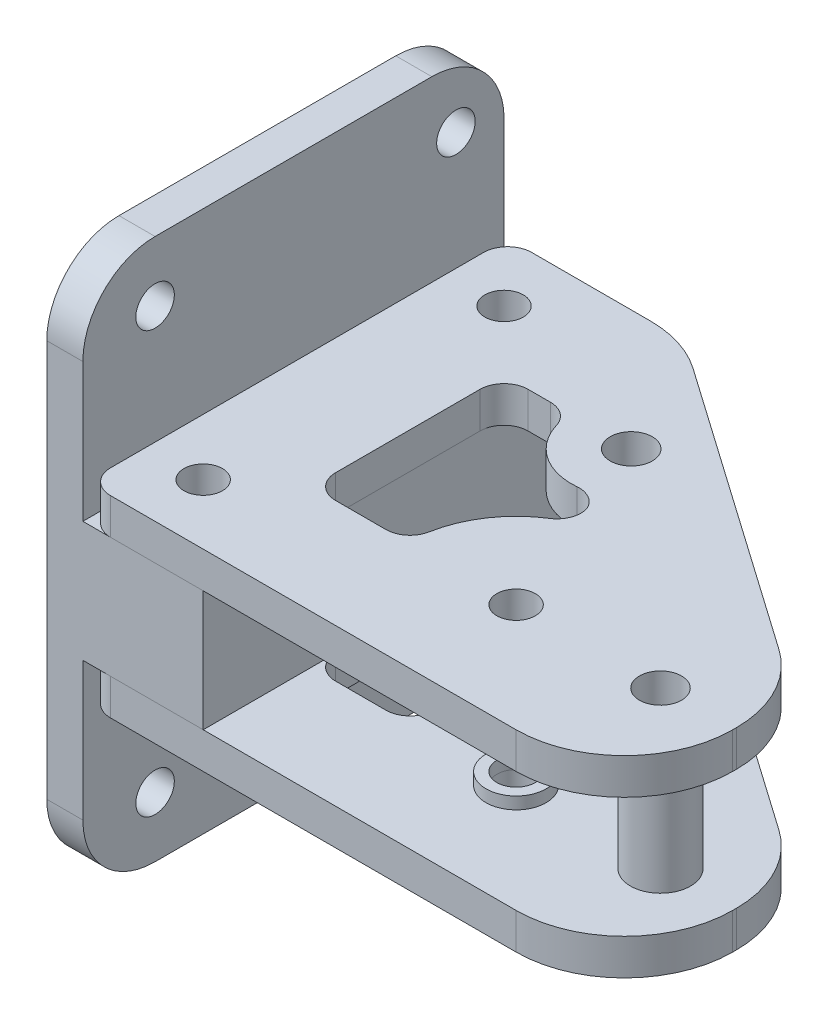
SolidWorks part; units mm, degrees
ref_plane "前视基准面" through (0, 0, 0) normal (0, 0, 1) x (1, 0, 0)
ref_plane "上视基准面" through (0, 0, 0) normal (0, 1, 0) x (1, 0, 0)
ref_plane "右视基准面" through (0, 0, 0) normal (1, 0, 0) x (0, 0, -1)
sketch "草图1" plane through (-18, 0, 0) normal (1, 0, 0) x (0, 0, -1)
  line L5 (-12.5, -18.5) -> (10.5, -18.5)
  line L6 (16.5, -12.5) -> (16.5, 20.5)
  line L7 (10.5, 26.5) -> (-12.5, 26.5)
  line L8 (-18.5, 20.5) -> (-18.5, -12.5)
  line L9 (-12.5, -18.5) -> (10.5, -18.5)
  line L10 (16.5, -12.5) -> (16.5, 20.5)
  line L11 (10.5, 26.5) -> (-12.5, 26.5)
  line L12 (-18.5, 20.5) -> (-18.5, -12.5)
  circle A0 centre (-12.5, -13.5) radius 1.6 construction
  circle A1 centre (12.5, -13.5) radius 1.6 construction
  circle A2 centre (12.5, 21.5) radius 1.6 construction
  circle A3 centre (-12.5, 21.5) radius 1.6 construction
  arc A4 (10.5, -18.5) -> (16.5, -12.5) centre (10.5, -12.5) ccw
  arc A5 (16.5, 20.5) -> (10.5, 26.5) centre (10.5, 20.5) ccw
  arc A6 (-12.5, 26.5) -> (-18.5, 20.5) centre (-12.5, 20.5) ccw
  arc A7 (-18.5, -12.5) -> (-12.5, -18.5) centre (-12.5, -12.5) ccw
  arc A8 (10.5, -18.5) -> (16.5, -12.5) centre (10.5, -12.5) ccw
  arc A9 (16.5, 20.5) -> (10.5, 26.5) centre (10.5, 20.5) ccw
  arc A10 (-12.5, 26.5) -> (-18.5, 20.5) centre (-12.5, 20.5) ccw
  arc A11 (-18.5, -12.5) -> (-12.5, -18.5) centre (-12.5, -12.5) ccw
  circle A12 centre (-12.5, -13.5) radius 1.6
  circle A13 centre (12.5, -13.5) radius 1.6
  circle A14 centre (12.5, 21.5) radius 1.6
  circle A15 centre (-12.5, 21.5) radius 1.6
  dimension "D1" = 0
extrude "凸台-拉伸1" add sketch "草图1" along normal blind 3
sketch "草图2" plane through (-15, 0, 0) normal (1, 0, 0) x (0, 0, -1)
  line L0 (-18.5, 4) -> (16.5, 4) construction
  line L1 (-18.5, 20.5) -> (-18.5, -12.5) construction
  line L2 (16.5, -12.5) -> (16.5, 20.5) construction
  line L3 (-1, 26.5) -> (-1, -18.5) construction
  line L4 (10.5, 26.5) -> (-12.5, 26.5) construction
  line L5 (-12.5, -18.5) -> (10.5, -18.5) construction
  line L7 (-18.5, -1) -> (16.5, -1)
  line L8 (-18.5, -1) -> (-18.5, 9)
  line L9 (-18.5, 9) -> (16.5, 9)
  line L10 (16.5, -1) -> (16.5, 9)
  line L11 (-18.5, -1) -> (16.5, 9) construction
  line L12 (-18.5, 9) -> (16.5, -1) construction
  point P12 (-1, 4)
  dimension "D1" = 10
extrude "凸台-拉伸2" add sketch "草图2" along normal blind 10
sketch "草图4" plane through (0, -1, 0) normal (0, -1, 0) x (1, 0, 0)
  line L0 (-10, 18.5) -> (-10, -16.5) construction
  line L1 (-5, 18.5) -> (-15, 18.5) construction
  line L2 (-5, -16.5) -> (-15, -16.5) construction
  line L3 (-5, 1) -> (-15, 1) construction
  line L4 (-5, 18.5) -> (-5, -16.5) construction
  line L5 (-15, 12.5) -> (-15, -10.5) construction
  circle A0 centre (-10, 13.5) radius 1.6
  circle A1 centre (-10, -11.5) radius 1.6
  dimension "D1" = 3.2
  dimension "D2" = 25
extrude "切除-拉伸2" cut sketch "草图4" against normal up to next
sketch "草图6" plane through (0, -1, 0) normal (0, -1, 0) x (1, 0, 0)
  line L0 (-15, 18.5) -> (30, 18.5)
  line L1 (30, 18.5) -> (30, 4.5)
  line L2 (30, 4.5) -> (0, -16.5)
  line L3 (0, -16.5) -> (-15, -16.5)
  line L4 (-15, -16.5) -> (-15, 18.5)
  line L5 (-5, 18.5) -> (-5, -16.5) construction
  circle A0 centre (-10, -11.5) radius 1.6 construction
  circle A2 centre (-10, 13.5) radius 1.6 construction
  circle A3 centre (-10, -11.5) radius 1.6
  circle A5 centre (-10, 13.5) radius 1.6
  dimension "D1" = 35
  dimension "D2" = 15
  dimension "D3" = 14
extrude "凸台-拉伸3" add sketch "草图6" along normal blind 3 separate body
sketch "草图7" plane through (0, -4, 0) normal (0, -1, 0) x (1, 0, 0)
  line L0 (30, 18.5) -> (-15, 18.5) construction
  line L3 (-18, 12.5) -> (-18, -10.5) construction
  circle A0 centre (12, 9.5) radius 1.6
  dimension "D2" = 3.2
  dimension "D1" = 9
  dimension "D3" = 30
extrude "切除-拉伸3" cut sketch "草图7" against normal up to next (3 mm away)
sketch "草图8" plane through (0, -4, 0) normal (0, -1, 0) x (1, 0, 0)
  line L0 (12, 9.5) -> (33.6436, 9.5) construction
  line L2 (30, 18.5) -> (-15, 18.5) construction
  line L3 (0, -16.5) -> (30, 4.5) construction
  circle A0 centre (24, 9.5) radius 1.75
  circle A1 centre (12, 9.5) radius 1.6 construction
  circle A2 centre (5.5667, -6.5) radius 1.75
  dimension "D1" = 12
  dimension "D2" = 3.5
  dimension "D3" = 5
  dimension "D4" = 25
extrude "切除-拉伸4" cut sketch "草图8" against normal up to next (3 mm away)
sketch "草图11" plane through (0, -4, 0) normal (0, -1, 0) x (1, 0, 0)
  line L0 (-15, -16.5) -> (0, -16.5) construction
  line L1 (-15, 18.5) -> (-14.7, 18.5)
  line L2 (-15, 18.5) -> (-15, -16.5)
  line L3 (-15, -16.5) -> (-14.7, -16.5)
  line L4 (-14.7, 18.5) -> (-14.7, -16.5)
  dimension "D1" = 0.3
extrude "切除-拉伸6" cut sketch "草图11" against normal up to next (3 mm away)
fillet "圆角2" radius 9 3 edges at (0, -2.5, -16.5) (30, -2.5, 4.5) (30, -2.5, 18.5)
fillet "圆角4" radius 2 2 edges at (-14.7, -2.5, -16.5) (-14.7, -2.5, 18.5)
sketch "草图12" plane through (0, -1, 0) normal (0, 1, 0) x (1, 0, 0)
  line L0 (0.5667, 6.5) -> (-5, 6.5)
  line L1 (-5, 16.5) -> (-5, -18.5) construction
  line L2 (-5, 6.5) -> (-5, -9.5)
  line L3 (-5, -9.5) -> (3, -9.5)
  line L4 (12, -9.5) -> (-0.8443, -9.5) construction
  line L5 (5.5667, 6.5) -> (12, -9.5)
  circle A0 centre (5.5667, 6.5) radius 5
  circle A1 centre (12, -9.5) radius 9
  dimension "D1" = 10
  dimension "D2" = 18
extrude "切除-拉伸9" cut sketch "草图12" against normal up to surface (3 mm away) contours A1 L5 A0 L0 L2 L3 region at (-0.0313, -1, 1.788) up to face at (25.75, -4, 9.5)
fillet "圆角5" radius 2 6 edges at (3, -2.5, 9.5) (-5, -2.5, 9.5) (-5, -2.5, -6.5) (0.5667, -2.5, -6.5) (7.432, -2.5, -1.8609) (8.6425, -2.5, 1.1497)
ref_plane "基准面1" through (0, 4, 0) normal (0, -1, 0) x (-1, 0, 0)
mirror "镜向1" about plane through (0, 4, 0) normal (0, -1, 0) of bodies 116
sketch "草图9" plane through (0, -1, 0) normal (0, 1, 0) x (1, 0, 0)
  circle A0 centre (24, -9.5) radius 1.75 construction
  circle A1 centre (24, -9.5) radius 1.75
  circle A2 centre (24, -9.5) radius 2.5
  dimension "D1" = 5
extrude "凸台-拉伸4" add sketch "草图9" along normal blind 10 separate body
sketch "草图13" plane through (0, -1, 0) normal (0, 1, 0) x (1, 0, 0)
  circle A0 centre (12, -9.5) radius 2.5
  circle A1 centre (12, -9.5) radius 1.6 construction
  circle A2 centre (12, -9.5) radius 1.6
  dimension "D1" = 5
extrude "凸台-拉伸5" add sketch "草图13" along normal blind 1 separate body
sketch "草图14" plane through (0, 9, 0) normal (0, -1, 0) x (1, 0, 0)
  circle A0 centre (12, 9.5) radius 1.6 construction
  circle A1 centre (12, 9.5) radius 2.5
  circle A2 centre (12, 9.5) radius 2.5
  circle A3 centre (12, 9.5) radius 1.6
  dimension "D1" = 0
extrude "凸台-拉伸6" add sketch "草图14" along normal blind 1 separate body
sketch "草图15" plane through (0, 12, 0) normal (0, 1, 0) x (1, 0, 0)
  line L0 (24.5494, 33.36) -> (12, -9.5) construction
  line L1 (12, -9.5) -> (-7.9712, -34.7245) construction
  line L3 (12, -9.5) -> (-21.0405, 7.5754) construction
  line L4 (21, -18.5) -> (-12.7, -18.5) construction
  dimension "D1" = 27.33
  dimension "D2" = 157.95
  dimension "D3" = 78.96
